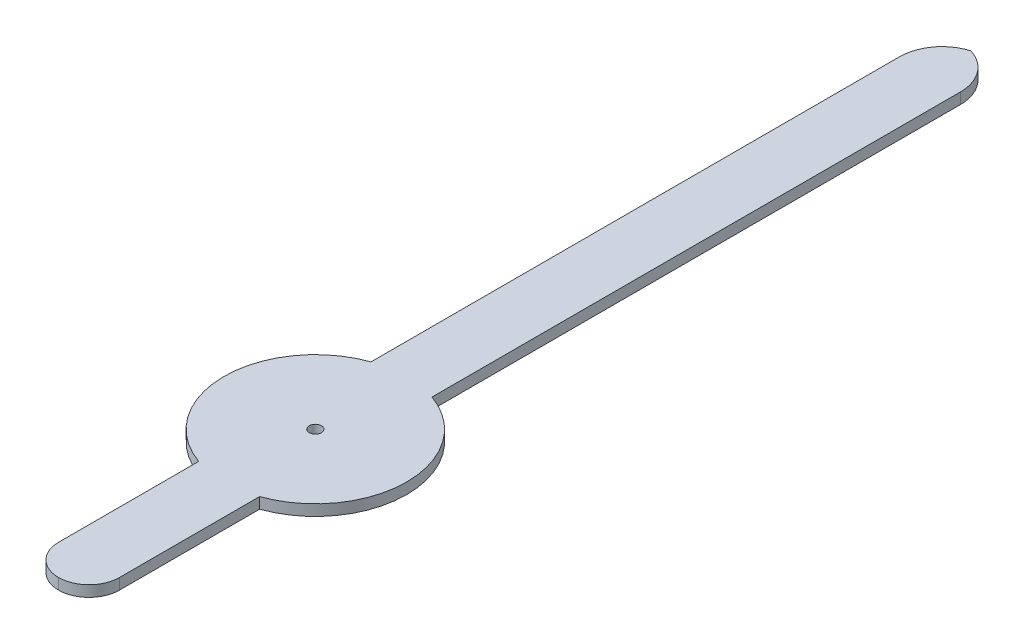
SolidWorks part; units mm, degrees
ref_plane "Front Plane" through (0, 0, 0) normal (0, 0, 1) x (1, 0, 0)
ref_plane "Top Plane" through (0, 0, 0) normal (0, 1, 0) x (1, 0, 0)
ref_plane "Right Plane" through (0, 0, 0) normal (1, 0, 0) x (0, 0, -1)
sketch "Sketch1" plane through (0, 0, 0) normal (0, 1, 0) x (1, 0, 0)
  line L0 (0, 0) -> (-0.1, 0) construction
  line L1 (-0.5, -4.2142) -> (-0.5, -1.4142)
  line L3 (0, -55) -> (0, 55) construction
  line L4 (0.5, -4.2142) -> (0.5, -1.4142)
  line L5 (0.5, 1.4142) -> (0.5, 10.7858)
  line L6 (-0.5, -4.2142) -> (0.5, -4.2142)
  line L7 (-0.5, 10.7858) -> (0.5, 10.7858)
  line L8 (-0.5, 1.4142) -> (-0.5, 10.7858)
  arc A0 (-0.5, 1.4142) -> (-0.5, -1.4142) centre (0, 0) ccw
  circle A1 centre (0, 0) radius 0.1
  arc A2 (0.5, -1.4142) -> (0.5, 1.4142) centre (0, 0) ccw
  dimension "D1" = 3
  dimension "D2" = 0.2
  dimension "D3" = 2.8
  dimension "D4" = 0.5
  dimension "D5" = 15
extrude "Boss-Extrude1" add sketch "Sketch1" along normal blind 0.18
fillet "Fillet1" radius 0.5 2 edges at (-0.5, 0.09, 4.2142) (0.5, 0.09, 4.2142)
fillet "Fillet2" radius 0.7 2 edges at (-0.5, 0.09, -10.7858) (0.5, 0.09, -10.7858)
